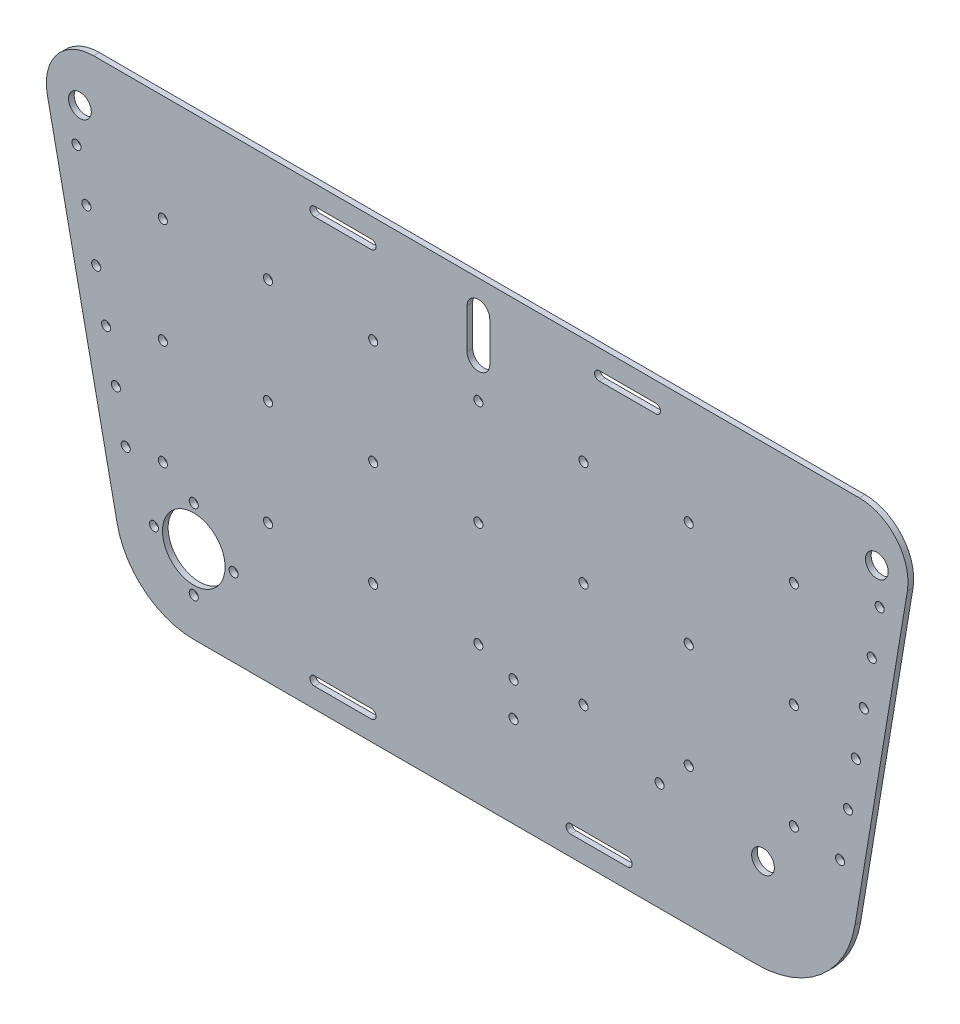
SolidWorks part; units mm, degrees
ref_plane "Front Plane" through (0, 0, 0) normal (0, 0, 1) x (1, 0, 0)
ref_plane "Top Plane" through (0, 0, 0) normal (0, 1, 0) x (1, 0, 0)
ref_plane "Right Plane" through (0, 0, 0) normal (1, 0, 0) x (0, 0, -1)
sketch "Sketch1" plane through (0, 0, 0) normal (0, 0, 1) x (1, 0, 0)
  line L1 (0, 0) -> (0, 115.062) construction
  line L2 (-140, 115.062) -> (140, 115.062) construction
  line L3 (-100, -37.4683) -> (100, -37.4683)
  line L4 (142.2945, 0.8576) -> (153.4347, 113.7361)
  line L5 (137.3964, 128.3085) -> (2.6036, 101.8154)
  line L6 (-2.6036, 101.8154) -> (-137.3964, 128.3085)
  line L7 (-153.3748, 113.2277) -> (-137.1523, -5.0634)
  line L8 (100, -34.9683) -> (-100, -34.9683) construction
  arc A12 (-137.1523, -5.0634) -> (-100, -37.4683) centre (-100, 0.0317) ccw
  arc A13 (100, -37.4683) -> (142.2945, 0.8576) centre (100, 5.0317) ccw
  arc A14 (153.4347, 113.7361) -> (137.3964, 128.3085) centre (140, 115.062) ccw
  arc A15 (2.6036, 101.8154) -> (-2.6036, 101.8154) centre (0, 115.062) cw
  arc A16 (-137.3964, 128.3085) -> (-153.3748, 113.2277) centre (-140, 115.062) ccw
  point P8 (0, 115.062)
  point P26 (0, -34.9683)
  circle B0 centre (-100, 0.0317) radius 35
  circle B1 centre (100, 5.0317) radius 40
  circle B2 centre (-140, 115.062) radius 11
  circle B3 centre (0, 115.062) radius 11
  circle B4 centre (140, 115.062) radius 11
  dimension "D1" = 200
  dimension "D3" = 280
  dimension "D7" = 279.5095
  dimension "D8" = 165.7768
sketch_block_instance "Block2-1"
sketch_block "Block2" parameters "D1"=52.784
sketch_block_instance "Block3-1"
sketch_block "Block3" parameters "D1"=49.6633
sketch_block_instance "Block4-1"
sketch_block "Block4"
sketch_block_instance "Block5-1"
sketch_block "Block5" parameters "D1"=22
sketch_block_instance "Block6-1"
sketch_block "Block6"
other "Belt1"
sketch "Sketch5" plane through (0, 0, 0) normal (0, 0, 1) x (1, 0, 0)
  line L12 (-100, -37.4683) -> (100, -37.4683) construction
  line L25 (110.1118, -2.4683) -> (77.5737, -2.4683)
  line L26 (65.3235, -2.4683) -> (34.5589, -2.4683)
  line L27 (134.4186, -22.4683) -> (143.6762, -22.4683)
  line L28 (143.4347, -2.4683) -> (134.6111, -2.4683)
  line L29 (143.4347, -2.4683) -> (143.4347, -22.4683)
  line L30 (16.6763, -22.4683) -> (134.2763, -22.4683)
  line L31 (15.513, -2.4683) -> (7.5179, -2.4683)
  line L32 (15.513, -22.4683) -> (7.5179, -22.4683)
  line L33 (7.5179, -2.4683) -> (7.5179, -22.4683)
  line L57 (14.6295, 0.5317) -> (66.6561, 0.5317)
  line L58 (66.6561, 0.5317) -> (66.6561, 7.0446)
  line L59 (66.6561, 14.0189) -> (66.6561, 20.5317)
  line L60 (66.6561, 20.5317) -> (14.6295, 20.5317)
  line L61 (10.0864, 20.5317) -> (8.6561, 20.5317)
  line L62 (8.6561, 20.5317) -> (8.6561, 19.2625)
  line L63 (8.6561, 13.801) -> (8.6561, 7.2625)
  line L64 (8.6561, 1.801) -> (8.6561, 0.5317)
  line L65 (8.6561, 0.5317) -> (10.0864, 0.5317)
  circle A0 centre (100, 5.0317) radius 11
  circle A2 centre (100, 5.0317) radius 7
  circle A29 centre (63.6561, 10.5317) radius 1.6
  circle A30 centre (12.3579, 16.5317) radius 1.6
  arc A36 (66.6561, 7.0446) -> (66.6561, 14.0189) centre (63.6561, 10.5317) ccw
  arc A37 (14.6295, 20.5317) -> (10.0864, 20.5317) centre (12.3579, 16.5317) ccw
  arc A38 (8.6561, 19.2625) -> (8.6561, 13.801) centre (12.3579, 16.5317) ccw
  arc A39 (8.6561, 7.2625) -> (8.6561, 1.801) centre (12.3579, 4.5317) ccw
  arc A40 (10.0864, 0.5317) -> (14.6295, 0.5317) centre (12.3579, 4.5317) ccw
  circle A41 centre (12.3579, 4.5317) radius 1.6
  dimension "D1" = 3.2
  dimension "D2" = 4.6
  dimension "D23" = 22
  dimension "D24" = 14
  dimension "D3" = 1.1383
  dimension "D4" = 2.5685
  dimension "D5" = 4.8401
  dimension "D6" = 136.1584
  dimension "D7" = 7.9951
  dimension "D8" = 9.1584
  dimension "D9" = 27.0411
  dimension "D10" = 56.1383
  dimension "D11" = 57.8057
  dimension "D12" = 59.1383
  dimension "D13" = 70.0559
  dimension "D14" = 102.594
  dimension "D15" = 126.7584
  dimension "D16" = 126.9007
  dimension "D17" = 127.0932
  dimension "D18" = 135.9169
  dimension "D19" = 20
  dimension "D20" = 23
  dimension "D21" = 29.5129
  dimension "D22" = 15
  dimension "D25" = 10
sketch "Sketch3" plane through (0, 0, 0) normal (0, 0, 1) x (1, 0, 0)
  line L0 (-100, -27.4683) -> (97.7714, -27.4683)
  line L1 (-100, -37.4683) -> (100, -37.4683) construction
  line L2 (-126.9257, -5.5588) -> (-151.4564, 112.5875)
  line L3 (132.3429, 1.8398) -> (150.7181, 112.5875)
  line L4 (-137.1523, -5.0634) -> (-126.9257, -5.5588) construction
  line L6 (142.2945, 0.8576) -> (132.3429, 1.8398) construction
  line L7 (142.2945, 0.8576) -> (153.4347, 113.7361) construction
  line L8 (-135.2278, 132.5317) -> (133.8103, 132.5317)
  line L9 (-4, 121.9902) -> (-4, 108.1338)
  line L10 (4, 121.9902) -> (4, 108.1338)
  circle A0 centre (-140, 115.062) radius 4
  circle A1 centre (0, 115.062) radius 4
  circle A2 centre (140, 115.062) radius 4
  circle A3 centre (100, 5.0317) radius 4
  circle A4 centre (-100, 0.0317) radius 11
  circle A6 centre (140, 115.062) radius 11 construction
  arc A7 (-100, -27.4683) -> (-126.9257, -5.5588) centre (-100, 0.0317) cw
  arc A8 (97.7714, -27.4683) -> (132.3429, 1.8398) centre (97.7714, 7.5758) ccw
  arc A10 (-151.4564, 112.5875) -> (-135.2278, 132.5317) centre (-135.2278, 115.9571) cw
  arc A11 (150.7181, 112.5875) -> (133.8103, 132.5317) centre (133.8103, 115.3929) ccw
  circle A13 centre (63.6561, 10.5317) radius 1.6 construction
  circle A14 centre (12.3579, 4.5317) radius 1.6 construction
  circle A15 centre (12.3579, 16.5317) radius 1.6 construction
  circle A16 centre (63.6561, 10.5317) radius 1.6
  circle A17 centre (12.3579, 4.5317) radius 1.6
  circle A18 centre (12.3579, 16.5317) radius 1.6
  circle A19 centre (-100, 0.0317) radius 14 construction
  circle A20 centre (-100, 14.0317) radius 1.6
  circle A21 centre (-86, 0.0317) radius 1.6
  circle A22 centre (-100, -13.9683) radius 1.6
  circle A23 centre (-114, 0.0317) radius 1.6
  circle A24 centre (0, 115.062) radius 8 construction
  arc A25 (-4, 121.9902) -> (4, 121.9902) centre (0, 121.9902) cw
  arc A26 (-4, 108.1338) -> (4, 108.1338) centre (0, 108.1338) ccw
  dimension "D1" = 8
  dimension "D5" = 22
  dimension "D6" = 28
  dimension "D7" = 3.2
  dimension "D2" = 10
  dimension "D3" = 10
  dimension "D4" = 160
  dimension "D9" = 8
  dimension "D8" = 4
extrude "Boss-Extrude1" add sketch "Sketch3" along normal blind 2 contours A10 L2 A7 L0 A8 L3 A11 L8 A26 L9 A25 L10 A23 A22 A21 A20 A18 A17 A16 A4 A3 A2 A0 region at (1.4431, 55.8088, 0)
sketch "Sketch6" plane through (0, 0, 0) normal (0, 0, 1) x (1, 0, 0)
  line L0 (-57.58, -17.2983) -> (-37.58, -17.2983)
  line L1 (-57.58, -20.4983) -> (-37.58, -20.4983)
  line L2 (32.42, -17.2983) -> (52.42, -17.2983)
  line L3 (32.42, -20.4983) -> (52.42, -20.4983)
  line L4 (-100, -27.4683) -> (97.7714, -27.4683) construction
  line L5 (32.42, -18.8983) -> (-37.58, -18.8983) construction
  line L6 (-25.08, -27.4683) -> (-25.08, 132.5317) construction
  line L7 (-135.2278, 132.5317) -> (133.8103, 132.5317) construction
  line L8 (-25.08, 52.5317) -> (-5.468, 52.5317) construction
  line L9 (-57.58, 125.5617) -> (-37.58, 125.5617)
  line L10 (-57.58, 122.3617) -> (-37.58, 122.3617)
  line L11 (42.42, 125.5617) -> (62.42, 125.5617)
  line L12 (42.42, 122.3617) -> (62.42, 122.3617)
  arc A0 (-57.58, -17.2983) -> (-57.58, -20.4983) centre (-57.58, -18.8983) ccw
  arc A1 (-37.58, -17.2983) -> (-37.58, -20.4983) centre (-37.58, -18.8983) cw
  arc A2 (52.42, -17.2983) -> (52.42, -20.4983) centre (52.42, -18.8983) cw
  arc A3 (32.42, -17.2983) -> (32.42, -20.4983) centre (32.42, -18.8983) ccw
  arc A4 (-37.58, 122.3617) -> (-37.58, 125.5617) centre (-37.58, 123.9617) ccw
  arc A5 (-57.58, 122.3617) -> (-57.58, 125.5617) centre (-57.58, 123.9617) cw
  arc A6 (42.42, 122.3617) -> (42.42, 125.5617) centre (42.42, 123.9617) cw
  arc A7 (62.42, 122.3617) -> (62.42, 125.5617) centre (62.42, 123.9617) ccw
  point P6 (-47.58, -17.2983)
  dimension "D1" = 3.2
  dimension "D2" = 52.42
  dimension "D3" = 20
  dimension "D5" = 8.57
  dimension "D6" = 2
  dimension "D7" = 70
  dimension "D4" = 2
extrude "Cut-Extrude3" cut sketch "Sketch6" along normal through all
ref_plane "Plane1" through (0, 52.5317, 0) normal (0, -1, 0) x (-1, 0, 0)
sketch "Sketch7" plane through (0, 0, 2) normal (0, 0, 1) x (1, 0, 0)
  line L0 (0, 95.0743) -> (0, 104.1338) construction
  line L1 (-88.8055, 84.3587) -> (-73.8055, 84.3587) construction
  line L2 (-88.8055, 84.3587) -> (-88.8055, 69.3587) construction
  line L3 (-88.8055, 69.3587) -> (-73.8055, 69.3587) construction
  line L4 (-73.8055, 84.3587) -> (-73.8055, 69.3587) construction
  line L5 (-88.8055, 84.3587) -> (-73.8055, 69.3587) construction
  line L6 (-88.8055, 69.3587) -> (-73.8055, 84.3587) construction
  line L7 (-141.1844, 102.4668) -> (-121.897, 9.5732) construction
  line L8 (-126.9257, -5.5588) -> (-151.4564, 112.5875) construction
  line L9 (-1.1, 52.5317) -> (1.1, 52.5317) construction
  line L10 (140.9921, 102.8439) -> (122.5363, -8.3891) construction
  line L12 (132.3429, 1.8398) -> (150.7181, 112.5875) construction
  circle A0 centre (-110.8622, 95.0743) radius 1.6
  circle A1 centre (-73.9081, 95.0743) radius 1.6
  circle A2 centre (-36.9541, 95.0743) radius 1.6
  circle A3 centre (0, 95.0743) radius 1.6
  circle A4 centre (36.9541, 95.0743) radius 1.6
  circle A5 centre (73.9081, 95.0743) radius 1.6
  circle A6 centre (110.8622, 95.0743) radius 1.6
  circle A7 centre (-73.9081, 58.0743) radius 1.6
  circle A8 centre (-36.9541, 58.0743) radius 1.6
  circle A9 centre (0, 58.0743) radius 1.6
  circle A10 centre (36.9541, 58.0743) radius 1.6
  circle A11 centre (73.9081, 58.0743) radius 1.6
  circle A12 centre (110.8622, 58.0743) radius 1.6
  circle A13 centre (-73.9081, 21.0743) radius 1.6
  circle A14 centre (-36.9541, 21.0743) radius 1.6
  circle A15 centre (0, 21.0743) radius 1.6
  circle A16 centre (36.9541, 21.0743) radius 1.6
  circle A17 centre (73.9081, 21.0743) radius 1.6
  circle A18 centre (110.8622, 21.0743) radius 1.6
  circle A19 centre (-110.8622, 58.0743) radius 1.6
  circle A20 centre (-110.8622, 21.0743) radius 1.6
  arc A21 (-4, 108.1338) -> (4, 108.1338) centre (0, 108.1338) ccw construction
  circle A22 centre (-141.1844, 102.4668) radius 1.6
  circle A23 centre (-137.7284, 85.8218) radius 1.6
  circle A24 centre (-134.2724, 69.1767) radius 1.6
  circle A25 centre (-130.8164, 52.5317) radius 1.6
  circle A26 centre (-127.3604, 35.8867) radius 1.6
  circle A27 centre (-123.9044, 19.2417) radius 1.6
  circle A28 centre (140.9921, 102.8439) radius 1.6
  circle A29 centre (138.2095, 86.0732) radius 1.6
  circle A30 centre (135.4269, 69.3025) radius 1.6
  circle A31 centre (132.6443, 52.5317) radius 1.6
  circle A32 centre (129.8617, 35.761) radius 1.6
  circle A33 centre (127.0791, 18.9903) radius 1.6
  point P0 (-81.3055, 76.8587)
  point P73 (0, 0)
  dimension "D1" = 3.2
  dimension "D4" = 6
  dimension "D6" = 8
  dimension "D2" = 7
  dimension "D5" = 8
  dimension "D3" = 3
  dimension "D7" = 6
extrude "Cut-Extrude4" cut sketch "Sketch7" against normal through all
